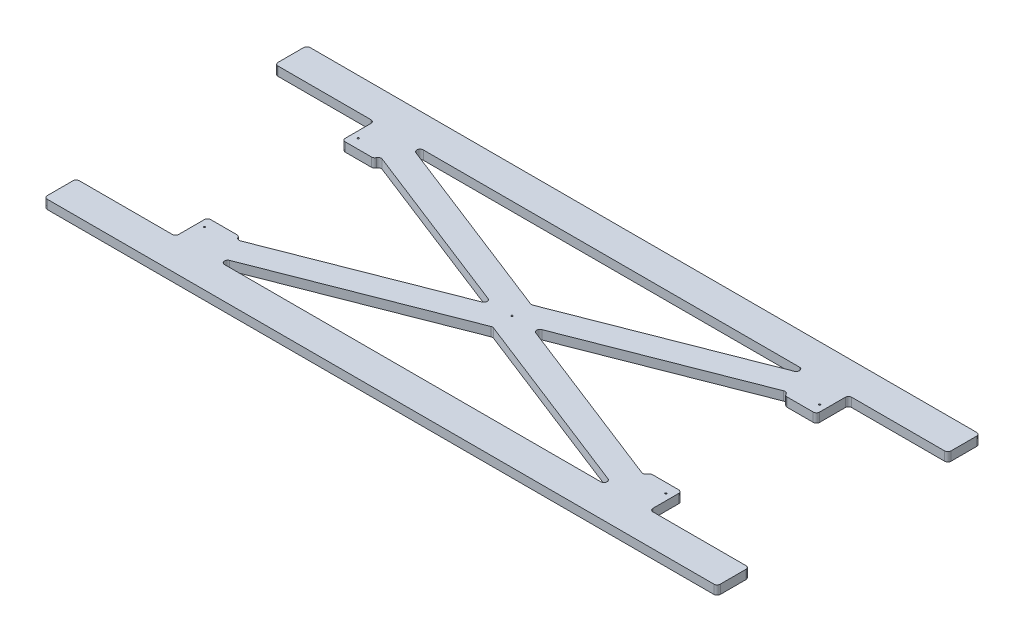
SolidWorks part; units mm, degrees
ref_plane "Front Plane" through (0, 0, 0) normal (0, 0, 1) x (1, 0, 0)
ref_plane "Top Plane" through (0, 0, 0) normal (0, 1, 0) x (1, 0, 0)
ref_plane "Right Plane" through (0, 0, 0) normal (1, 0, 0) x (0, 0, -1)
sketch "Sketch1" plane through (0, 0, 0) normal (0, 1, 0) x (1, 0, 0)
  line L1 (-666.75, 260.35) -> (666.75, 260.35)
  line L2 (-666.75, 260.35) -> (-666.75, -260.35)
  line L3 (-666.75, -260.35) -> (666.75, -260.35)
  line L4 (666.75, 260.35) -> (666.75, -260.35)
  line L5 (-666.75, 260.35) -> (666.75, -260.35) construction
  line L6 (-666.75, -260.35) -> (666.75, 260.35) construction
  point P0 (0, 0)
  dimension "D1" = 520.7
  dimension "D2" = 1333.5
extrude "Boss-Extrude1" add sketch "Sketch1" along normal blind 17.78
fillet "Fillet1" radius 6.35 4 edges at (-666.75, 8.89, 260.35) (-666.75, 8.89, -260.35) (666.75, 8.89, -260.35) (666.75, 8.89, 260.35)
hole_wizard "1/8 (0.125) Diameter Hole1" positions "Sketch3" profile "Sketch4" hole size "1/8" standard "ANSI Inch" end condition through all
sketch "Sketch3" plane through (0, 17.78, 0) normal (0, 1, 0) x (1, 0, 0)
  line L1 (-457.2, -152.4) -> (457.2, -152.4) construction
  line L2 (-457.2, -152.4) -> (-457.2, 152.4) construction
  line L3 (-457.2, 152.4) -> (457.2, 152.4) construction
  line L4 (457.2, -152.4) -> (457.2, 152.4) construction
  line L5 (-457.2, -152.4) -> (457.2, 152.4) construction
  line L6 (-457.2, 152.4) -> (457.2, -152.4) construction
  point P0 (0, 0)
  point P1 (457.2, 152.4)
  point P32 (-457.2, -152.4)
  point P33 (-457.2, 152.4)
  point P34 (457.2, -152.4)
  dimension "D1" = 914.4
  dimension "D2" = 304.8
sketch "Sketch4" plane through (0, 17.78, 0) normal (1, 0, 0) x (0, 0, 1)
  line L0 (0, 0) -> (0, 17.78)
  line L1 (0, 17.78) -> (1.5875, 17.78)
  line L2 (1.5875, 17.78) -> (1.5875, 0)
  line L5 (1.5875, 0) -> (0, 0)
  line L11 (0, -6.35) -> (0, 107.95) construction
  dimension "Thru Hole Dia." = 3.175
  dimension "Thru Hole Depth" = 17.78
sketch "Sketch2" plane through (0, 17.78, 0) normal (0, 1, 0) x (1, 0, 0)
  line L1 (-635, -330.2) -> (635, -330.2)
  line L2 (-635, -330.2) -> (-635, 330.2)
  line L3 (-635, 330.2) -> (635, 330.2)
  line L4 (635, -330.2) -> (635, 330.2)
  line L5 (-635, -330.2) -> (635, 330.2) construction
  line L6 (-635, 330.2) -> (635, -330.2) construction
  point P0 (0, 0)
  dimension "D1" = 660.4
  dimension "D2" = 1270
extrude "Boss-Extrude2" [suppressed] add sketch "Sketch2" along normal blind 9.525
sketch "Sketch5" plane through (0, 17.78, 0) normal (0, 1, 0) x (1, 0, 0)
  line L0 (-406.4, 196.85) -> (406.4, 196.85)
  line L1 (660.4, 260.35) -> (-660.4, 260.35) construction
  line L2 (0, 38.1) -> (-406.4, 196.85)
  line L3 (406.4, 196.85) -> (0, 38.1)
  line L4 (0, 260.35) -> (0, -260.35) construction
  line L5 (-660.4, -260.35) -> (660.4, -260.35) construction
  line L6 (-666.75, 0) -> (666.75, 0) construction
  line L7 (-666.75, 254) -> (-666.75, -254) construction
  line L8 (666.75, -254) -> (666.75, 254) construction
  line L9 (0, -38.1) -> (-406.4, -196.85)
  line L10 (-406.4, -196.85) -> (406.4, -196.85)
  line L11 (406.4, -196.85) -> (0, -38.1)
  line L12 (406.4, 143.8672) -> (406.4, -143.8672)
  line L13 (406.4, -143.8672) -> (38.1, 0)
  line L14 (406.4, 143.8672) -> (38.1, 0)
  line L15 (-406.4, 143.8672) -> (-38.1, 0)
  line L16 (-406.4, 143.8672) -> (-406.4, -143.8672)
  line L17 (-406.4, -143.8672) -> (-38.1, 0)
  line L18 (622.3, -196.85) -> (469.9, -196.85)
  line L19 (-622.3, -196.85) -> (-469.9, -196.85)
  line L20 (-622.3, -196.85) -> (-622.3, 196.85)
  line L21 (-622.3, 196.85) -> (-469.9, 196.85)
  line L22 (-469.9, -196.85) -> (-469.9, 196.85)
  line L23 (-622.3, -196.85) -> (-469.9, 196.85) construction
  line L24 (-622.3, 196.85) -> (-469.9, -196.85) construction
  line L25 (622.3, -196.85) -> (622.3, 196.85)
  line L26 (622.3, 196.85) -> (469.9, 196.85)
  line L27 (469.9, -196.85) -> (469.9, 196.85)
  circle A0 centre (0, 0) radius 38.1 construction
  point P3 (0, 196.85)
  point P30 (-546.1, 0)
  dimension "D2" = 76.2
  dimension "D4" = 152.4
  dimension "D1" = 63.5
  dimension "D3" = 812.8
  dimension "D5" = 44.45
extrude "Cut-Extrude1" cut sketch "Sketch5" against normal through all
fillet "Fillet2" radius 6.35 20 edges at (469.9, 8.89, -196.85) (469.9, 8.89, 196.85) (622.3, 8.89, 196.85) (406.4, 8.89, 143.8672) (406.4, 8.89, 196.85) (622.3, 8.89, -196.85) (406.4, 8.89, -143.8672) (406.4, 8.89, -196.85) (38.1, 8.89, 0) (0, 8.89, 38.1) (0, 8.89, -38.1) (-38.1, 8.89, 0) (-406.4, 8.89, 196.85) (-406.4, 8.89, -196.85) (-406.4, 8.89, -143.8672) (-406.4, 8.89, 143.8672) (-622.3, 8.89, 196.85) (-469.9, 8.89, 196.85) (-469.9, 8.89, -196.85) (-622.3, 8.89, -196.85)
sketch "Sketch6" plane through (0, 17.78, 0) normal (0, 1, 0) x (1, 0, 0)
  line L0 (666.75, -254) -> (666.75, 254) construction
  line L1 (615.95, -196.85) -> (666.75, -196.85)
  line L2 (615.95, -196.85) -> (615.95, 196.85)
  line L3 (615.95, 196.85) -> (666.75, 196.85)
  line L4 (666.75, -196.85) -> (666.75, 196.85)
  line L5 (-666.75, 254) -> (-666.75, -254) construction
  line L6 (-615.95, -196.85) -> (-666.75, -196.85)
  line L7 (-615.95, -196.85) -> (-615.95, 196.85)
  line L8 (-615.95, 196.85) -> (-666.75, 196.85)
  line L9 (-666.75, -196.85) -> (-666.75, 196.85)
  line L10 (-666.75, 0) -> (666.75, 0) construction
  line L11 (-469.9, -190.5) -> (-469.9, 190.5) construction
  line L12 (-469.9, -133.35) -> (-406.4, -133.35)
  line L13 (-469.9, -133.35) -> (-469.9, 133.35)
  line L14 (-469.9, 133.35) -> (-406.4, 133.35)
  line L15 (-406.4, -133.35) -> (-406.4, 133.35)
  line L16 (-469.9, -133.35) -> (-406.4, 133.35) construction
  line L17 (-469.9, 133.35) -> (-406.4, -133.35) construction
  line L18 (406.4, -133.35) -> (469.9, -133.35)
  line L19 (406.4, -133.35) -> (406.4, 133.35)
  line L20 (406.4, 133.35) -> (469.9, 133.35)
  line L21 (469.9, -133.35) -> (469.9, 133.35)
  line L22 (406.4, -133.35) -> (469.9, 133.35) construction
  line L23 (406.4, 133.35) -> (469.9, -133.35) construction
  line L24 (-406.4, 134.5694) -> (-406.4, -134.5694) construction
  line L25 (406.4, -134.5694) -> (406.4, 134.5694) construction
  line L26 (469.9, 190.5) -> (469.9, -190.5) construction
  point P16 (-438.15, 0)
  point P21 (438.15, 0)
  point P34 (0, 0)
  point P35 (0, 0)
  point P36 (0, 0)
  dimension "D1" = 266.7
extrude "Cut-Extrude2" cut sketch "Sketch6" against normal through all
fillet "Fillet3" radius 6.35 12 edges at (-666.75, 8.89, 196.85) (-666.75, 8.89, -196.85) (666.75, 8.89, -196.85) (666.75, 8.89, 196.85) (-406.4, 8.89, 133.35) (-406.4, 8.89, -133.35) (-469.9, 8.89, 133.35) (-469.9, 8.89, -133.35) (469.9, 8.89, -133.35) (406.4, 8.89, -133.35) (469.9, 8.89, 133.35) (406.4, 8.89, 133.35)
